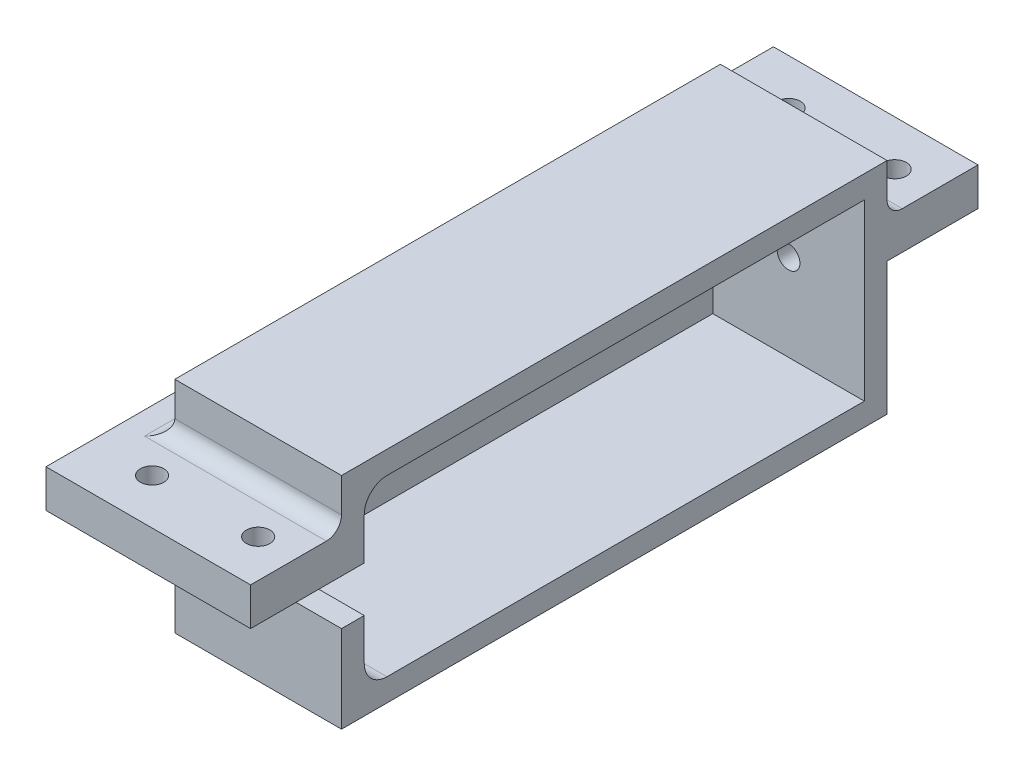
SolidWorks part; units mm, degrees
ref_plane "前基準面" through (0, 0, 0) normal (0, 0, 1) x (1, 0, 0)
ref_plane "上基準面" through (0, 0, 0) normal (0, 1, 0) x (1, 0, 0)
ref_plane "右基準面" through (0, 0, 0) normal (1, 0, 0) x (0, 0, -1)
sketch "草圖1" plane through (0, 0, 0) normal (1, 0, 0) x (0, 0, -1)
  line L1 (-30, 11.5) -> (33, 11.5)
  line L2 (-33, 8.5) -> (-33, -8.5)
  line L3 (-30, -11.5) -> (33, -11.5)
  line L4 (33, 11.5) -> (33, -11.5)
  line L5 (-33, 11.5) -> (33, -11.5) construction
  line L6 (-33, -11.5) -> (33, 11.5) construction
  line L7 (-36, 14.5) -> (36, 14.5)
  line L8 (-36, 14.5) -> (-36, -14.5)
  line L9 (-36, -14.5) -> (36, -14.5)
  line L10 (36, 14.5) -> (36, -14.5)
  line L11 (-36, 14.5) -> (36, -14.5) construction
  line L12 (-36, -14.5) -> (36, 14.5) construction
  arc A0 (-33, -8.5) -> (-30, -11.5) centre (-30, -8.5) ccw
  arc A1 (-30, 11.5) -> (-33, 8.5) centre (-30, 8.5) ccw
  point P0 (0, 0)
  point P6 (0, 0)
  dimension "D5" = 3
  dimension "D1" = 23
  dimension "D2" = 66
  dimension "D3" = 3
  dimension "D4" = 3
extrude "填料-伸長1" add sketch "草圖1" along normal blind 20
sketch "草圖2" plane through (0, 0, 36) normal (0, 0, 1) x (1, 0, 0)
  line L0 (0, 0) -> (20, 0) construction
  line L1 (0, 14.5) -> (0, -14.5) construction
  line L2 (20, 14.5) -> (20, -14.5) construction
  line L4 (0, 3) -> (11, 3)
  line L5 (0, 3) -> (0, -3)
  line L6 (0, -3) -> (11, -3)
  line L7 (11, 3) -> (11, -3)
  dimension "D1" = 11
  dimension "D2" = 3
  dimension "D3" = 3
extrude "除料-伸長1" cut sketch "草圖2" against normal up to next
sketch "草圖3" plane through (0, 0, -36) normal (0, 0, -1) x (-1, 0, 0)
  line L0 (0, 0) -> (-20, 0) construction
  line L1 (0, -14.5) -> (0, 14.5) construction
  line L2 (-20, -14.5) -> (-20, 14.5) construction
  circle A0 centre (-10, 0) radius 1.5
  dimension "D1" = 3
extrude "除料-伸長2" cut sketch "草圖3" against normal up to next
sketch "草圖4" plane through (20, 0, 0) normal (1, 0, 0) x (0, 0, -1)
  line L0 (-36, -14.5) -> (36, -14.5) construction
  line L1 (-36, 14.5) -> (36, 14.5)
  line L2 (-36, 14.5) -> (-36, -14.5)
  line L3 (-36, -14.5) -> (36, -14.5)
  line L4 (36, 14.5) -> (36, -14.5)
  line L5 (0, 0) -> (-36, 0) construction
  line L6 (-25, 3.5) -> (-18, 3.5) construction
  line L7 (-25, 3.5) -> (-25, -3.5) construction
  line L8 (-25, -3.5) -> (-18, -3.5) construction
  line L9 (-18, 3.5) -> (-18, -3.5) construction
  line L10 (-25, 3.5) -> (-18, -3.5) construction
  line L11 (-25, -3.5) -> (-18, 3.5) construction
  line L14 (36, -14.5) -> (36, 14.5) construction
  line L15 (-33, 8.5) -> (-33, -8.5) construction
  line L16 (-13, 2.5) -> (-8, 2.5)
  line L17 (-13, 2.5) -> (-13, -2.5)
  line L18 (-13, -2.5) -> (-8, -2.5)
  line L19 (-8, 2.5) -> (-8, -2.5)
  line L20 (-13, 2.5) -> (-8, -2.5) construction
  line L21 (-13, -2.5) -> (-8, 2.5) construction
  line L22 (0, 0) -> (36, 0) construction
  line L23 (7, 3.5) -> (12, 3.5)
  line L24 (7, 3.5) -> (7, -3.5)
  line L25 (7, -3.5) -> (12, -3.5)
  line L26 (12, 3.5) -> (12, -3.5)
  line L27 (7, 3.5) -> (12, -3.5) construction
  line L28 (7, -3.5) -> (12, 3.5) construction
  circle A1 centre (-21.5, 0) radius 3.5
  point P7 (-21.5, 0)
  point P18 (-10.5, 0)
  point P24 (9.5, 0)
  dimension "D1" = 25
  dimension "D2" = 15
  dimension "D3" = 7
  dimension "D4" = 7
  dimension "D5" = 5
  dimension "D6" = 5
  dimension "D7" = 45
  dimension "D8" = 40
  dimension "D9" = 7
extrude "填料-伸長2" add sketch "草圖4" along normal blind 2
sketch "草圖6" plane through (0, 0, 36) normal (0, 0, 1) x (1, 0, 0)
  line L0 (0, 14.5) -> (0, 3) construction
  line L1 (0, 8) -> (22, 8)
  line L2 (0, 8) -> (0, 3)
  line L3 (0, 3) -> (22, 3)
  line L4 (22, 8) -> (22, 3)
  line L5 (22, 14.5) -> (22, -14.5) construction
  line L6 (11, 3) -> (0, 3) construction
  dimension "D1" = 5
extrude "填料-伸長3" add sketch "草圖6" along normal blind 12
sketch "草圖7" plane through (0, 0, -36) normal (0, 0, -1) x (-1, 0, 0)
  line L0 (-22, -14.5) -> (-22, 14.5) construction
  line L1 (-22, 8) -> (0, 8)
  line L2 (-22, 8) -> (-22, 3)
  line L3 (-22, 3) -> (0, 3)
  line L4 (0, 8) -> (0, 3)
  line L5 (0, -14.5) -> (0, 14.5) construction
  line L6 (-22, 14.5) -> (0, 14.5) construction
  dimension "D1" = 5
  dimension "D2" = 11.5
extrude "填料-伸長4" add sketch "草圖7" along normal blind 12
sketch "草圖9" plane through (22, 0, 0) normal (1, 0, 0) x (0, 0, -1)
  line L0 (48, 8) -> (36, 8) construction
  line L1 (-48, 3) -> (-23.3028, 3)
  line L2 (-48, 3) -> (-48, 8)
  line L3 (-48, 8) -> (48, 8)
  line L4 (48, 3) -> (48, 8)
  line L6 (-19.6972, 3) -> (48, 3)
  line L7 (-48, 3) -> (-48, 8) construction
  line L8 (48, 8) -> (48, 3) construction
  circle A0 centre (-21.5, 0) radius 3.5 construction
  arc A1 (-19.6972, 3) -> (-23.3028, 3) centre (-21.5, 0) ccw
extrude "填料-伸長5" add sketch "草圖9" along normal blind 5
sketch "草圖10" plane through (0, 8, 0) normal (0, 1, 0) x (1, 0, 0)
  line L0 (0, -42) -> (27, -42) construction
  line L1 (0, -48) -> (0, -36) construction
  line L2 (27, 48) -> (27, -48) construction
  line L3 (0, 0) -> (27, 0) construction
  circle A0 centre (5, -42) radius 1.55
  circle A1 centre (19, -42) radius 1.55
  circle A2 centre (19, 42) radius 1.55
  circle A3 centre (5, 42) radius 1.55
  dimension "D1" = 3.1
  dimension "D2" = 3.1
  dimension "D3" = 5
  dimension "D4" = 8
extrude "除料-伸長4" cut sketch "草圖10" against normal up to next
fillet "圓角1" radius 2 3 edges at (11, 8, 36) (11, 8, -36) (22, 8, 0)
ref_plane "平面1" through (0, 0, 0) normal (-1, 0, 0) x (0, 0, 1)
mirror "鏡射4" about plane through (0, 0, 0) normal (-1, 0, 0) of "圓角1", "除料-伸長4", "填料-伸長5", "填料-伸長3", "填料-伸長4", "填料-伸長2", "除料-伸長2", "除料-伸長1", "填料-伸長1"
sketch "草圖11" plane through (0, 0, 0) normal (-1, 0, 0) x (0, 0, 1)
  line L1 (76.9785, 32.1995) -> (-75.961, 32.1995)
  line L2 (76.9785, 32.1995) -> (76.9785, -36.2534)
  line L3 (76.9785, -36.2534) -> (-75.961, -36.2534)
  line L4 (-75.961, 32.1995) -> (-75.961, -36.2534)
extrude "除料-伸長5" cut sketch "草圖11" against normal up to surface (27 mm away) up to face at (27, 4.75, 7.1667)
